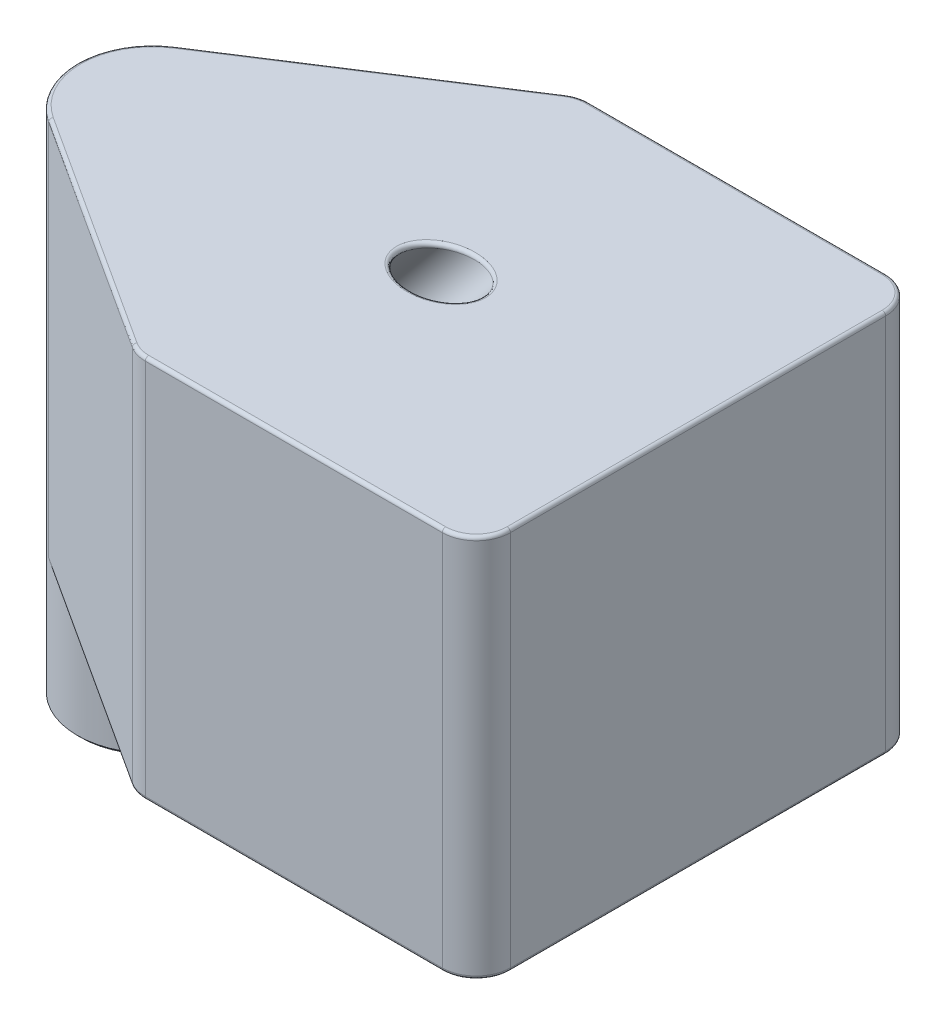
SolidWorks part; units mm, degrees
ref_plane "Front Plane" through (0, 0, 0) normal (0, 0, 1) x (1, 0, 0)
ref_plane "Top Plane" through (0, 0, 0) normal (0, 1, 0) x (1, 0, 0)
ref_plane "Right Plane" through (0, 0, 0) normal (1, 0, 0) x (0, 0, -1)
sketch "Sketch1" plane through (0, 0, 0) normal (0, 1, 0) x (1, 0, 0)
  circle A0 centre (0, 0) radius 2.2
  dimension "D1" = 4.4
extrude "Boss-Extrude1" add sketch "Sketch1" along normal blind 15
sketch "Sketch2" plane through (0, 0, 0) normal (0, -1, 0) x (1, 0, 0)
  line L1 (6.2952, 6.5) -> (15, 6.5)
  line L2 (16, 5.5) -> (16, -5.5)
  line L3 (15, -6.5) -> (6.2952, -6.5)
  line L5 (0, 0) -> (15.8849, 0) construction
  line L6 (-1.1947, 1.8474) -> (5.7521, 6.3397)
  line L7 (-1.1947, -1.8474) -> (5.7521, -6.3397)
  circle A0 centre (0, 0) radius 2.2 construction
  arc A1 (-1.1947, 1.8474) -> (-1.1947, -1.8474) centre (0, 0) ccw
  arc A2 (6.2952, -6.5) -> (5.7521, -6.3397) centre (6.2952, -5.5) cw
  arc A3 (16, -5.5) -> (15, -6.5) centre (15, -5.5) cw
  arc A4 (15, 6.5) -> (16, 5.5) centre (15, 5.5) cw
  arc A5 (5.7521, 6.3397) -> (6.2952, 6.5) centre (6.2952, 5.5) cw
  point P13 (6, -6.5)
  point P16 (16, -6.5)
  point P19 (16, 6.5)
  dimension "D4" = 16
  dimension "D5" = 1
  dimension "D1" = 13
  dimension "D2" = 10
  dimension "D3" = 6.5
extrude "Boss-Extrude2" add sketch "Sketch2" against normal up to surface (11.25 mm away) from offset 3.75 up to face at (0, 15, 2.2) offset against normal yes
sketch "Sketch3" [suppressed] plane through (0, 0, 0) normal (0, 0, 1) x (1, 0, 0)
  line L0 (-1.5, 0) -> (6.2221, 13.375) construction
  line L1 (-1.5, 0) -> (1.5, 0) construction
  line L2 (-2.1495, 0.375) -> (-1.5, 0)
  line L3 (-2.1495, 0.375) -> (5.5725, 13.75)
  line L4 (5.5725, 13.75) -> (6.2221, 13.375)
  line L5 (6.2221, 13.375) -> (6.8716, 13) construction
  line L6 (-0.9137, 13) -> (-1.5, 13) construction
  line L7 (-1.5, 0) -> (6.2221, 13.375) construction
  dimension "D1" = 60
  dimension "D2" = 0.75
  dimension "D3" = 0.75
revolve "Cut-Revolve1" [suppressed] cut sketch "Sketch3" angle 360 about L0
chamfer "Chamfer1" [suppressed] distance 0.1 angle 45
fillet "Fillet1" radius 0.1 10 edges at (2.2787, 15, -4.0935) (6.0121, 15, -6.4591) (10.6476, 15, -6.5) (15.7071, 15, -6.2071) (16, 15, 0) (15.7071, 15, 6.2071) (10.6476, 15, 6.5) (6.0121, 15, 6.4591) (2.2787, 15, 4.0935) (-2.2, 15, 0)
fillet "Fillet2" radius 0.1 9 edges at (2.2787, 3.75, 4.0935) (6.0121, 3.75, 6.4591) (10.6476, 3.75, 6.5) (15.7071, 3.75, 6.2071) (16, 3.75, 0) (15.7071, 3.75, -6.2071) (10.6476, 3.75, -6.5) (6.0121, 3.75, -6.4591) (2.2787, 3.75, -4.0935)
sketch "Sketch4" plane through (0, 0, 0) normal (0, 0, 1) x (1, 0, 0)
  line L0 (-1.5, 3.0246) -> (8.5485, 15) construction
  line L1 (6.2952, 15) -> (5.8064, 15) construction
  line L2 (-2.2, 0) -> (2.2, 0) construction
  line L3 (-2.1894, 3.6031) -> (-4.1178, 1.305)
  line L4 (-2.1894, 3.6031) -> (10.6716, 18.9304)
  line L5 (10.6716, 18.9304) -> (11.3611, 18.3518)
  line L6 (-1.5, 3.0246) -> (11.3611, 18.3518)
  line L7 (-4.1178, 1.305) -> (-3.4284, 0.7265)
  line L8 (-3.4284, 0.7265) -> (-1.5, 3.0246)
  line L9 (5.8064, 3.75) -> (-0.5897, 3.75) construction
  line L10 (-2.15, -0.1185) -> (-2.15, 6.4351) construction
  point P2 (-2.15, 2.25)
  dimension "D1" = 50
  dimension "D2" = 1.5
  dimension "D3" = 0.9
  dimension "D4" = 1.5
  dimension "D5" = 0.9
  dimension "D6" = 3
  dimension "D7" = 20.0082
  dimension "D8" = 2.15
revolve "Cut-Revolve2" cut sketch "Sketch4" angle 360 about L0
chamfer "Chamfer2" distance 0.1 angle 45 1 edges at (0, 0, 2.2)
fillet "Fillet3" [suppressed] radius 0.1
fillet "Fillet4" radius 0.1 1 edges at (7.3737, 15, 0)
fillet "Fillet5" radius 0.1 1 edges at (-2.1992, 3.5885, -0.0585)
sketch "Sketch6" plane through (0, 0, 0) normal (0, 0, 1) x (1, 0, 0)
  line L1 (-2.15, 2.25) -> (6.782, 12.8947) construction
  line L2 (-2.1, 0) -> (2.1, 0) construction
  line L3 (-0.5897, 3.75) -> (5.8064, 3.75) construction
  point P0 (-2.15, 2.25)
  dimension "D1" = 2.15
  dimension "D2" = 50
  dimension "D3" = 1.5
